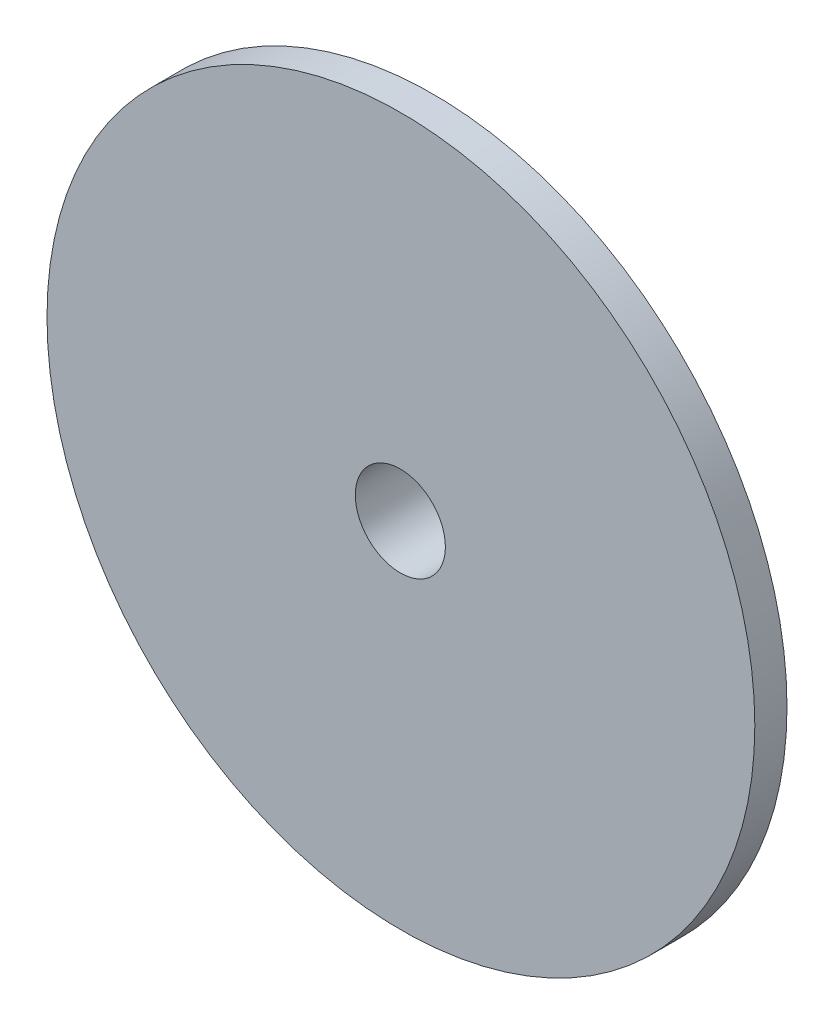
SolidWorks part; units mm, degrees
note: The reader was unsure of these and kept them because the rebuilt part matched: shared geometry of "Sketch1<3>".
ref_plane "Front Plane" through (0, 0, 0) normal (0, 0, 1) x (1, 0, 0)
ref_plane "Top Plane" through (0, 0, 0) normal (0, 1, 0) x (1, 0, 0)
ref_plane "Right Plane" through (0, 0, 0) normal (1, 0, 0) x (0, 0, -1)
sketch "Sketch1" plane through (0, 0, 0) normal (0, 0, 1) x (1, 0, 0)
  line L0 (0.09, 0) -> (-46.1619, 19.2109) construction
  circle A0 centre (0, 0) radius 50 construction
  arc A1 (-50.6932, 21.1203) -> (50.8441, 21.1902) centre (0.09, 0) ccw
  circle A2 centre (-46.1636, 19.2074) radius 4
  arc A3 (-28.7441, -27.9068) -> (-0.5059, 39.9068) centre (0, -0.09) ccw
  arc A4 (-28.7441, -27.9068) -> (-0.5059, 39.9068) centre (-120.6998, 50.1704) ccw
  circle A5 centre (0.09, 0) radius 55
  line B0 (-1.6504, 0) -> (1.6504, 0)
  line B1 (0, -1.6504) -> (0, 1.6504)
  line B2 (-16.624, 0) -> (-3.3008, 0) construction
  line B3 (3.3008, 0) -> (16.624, 0) construction
  line B4 (0, -16.624) -> (0, -3.3008) construction
  line B5 (0, 3.3008) -> (0, 16.624) construction
sketch_block_instance "*U0-1"
sketch_block "*U0"
extrude "Boss-Extrude1" add sketch "Sketch1" against normal blind 10
extrude "Boss-Extrude2" add sketch "Sketch1<3>" along normal blind 5 contours A5
sketch "Sketch1<3>" plane through (0, 0, 0) normal (0, 0, 1) x (1, 0, 0) same geometry as "Sketch1"
sketch "Sketch2" plane through (0, 0, 5) normal (0, 0, 1) x (1, 0, 0)
  circle A0 centre (0, 0) radius 7
  dimension "D1" = 14
extrude "Cut-Extrude1" cut sketch "Sketch2" against normal through all
